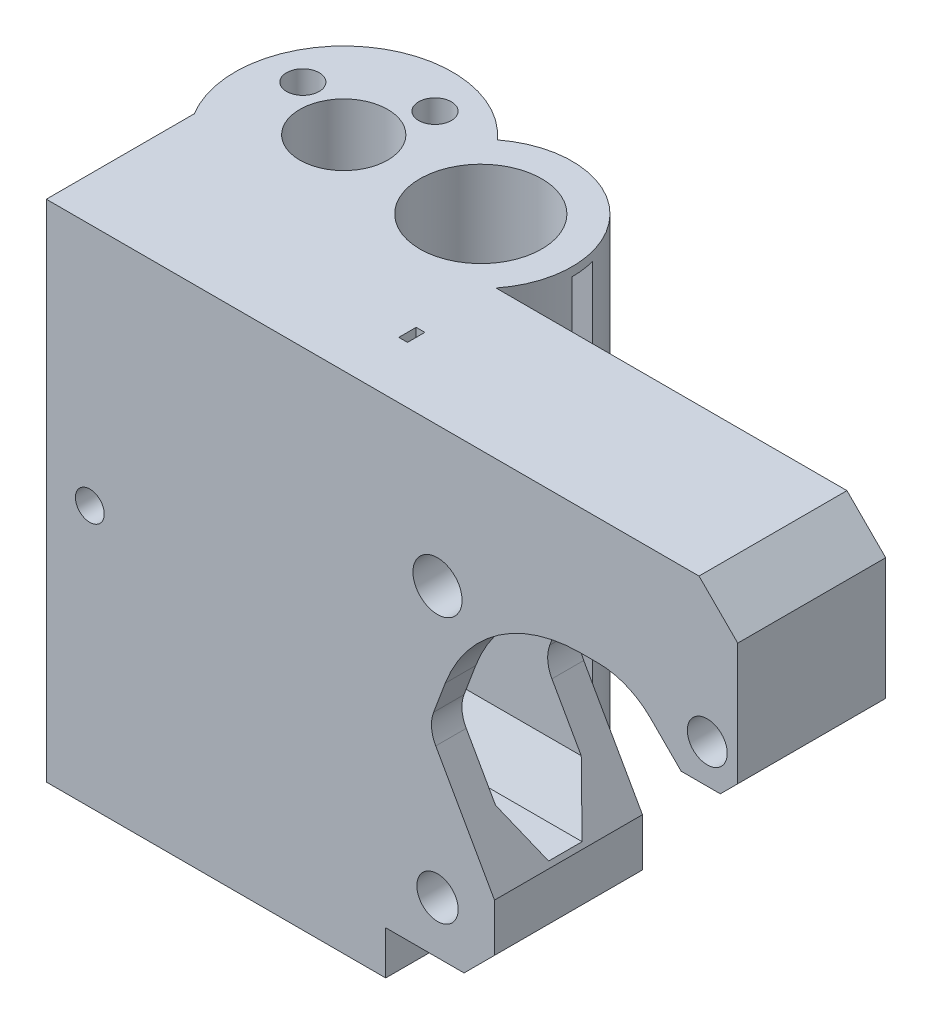
SolidWorks part; units mm, degrees
ref_plane "Front Plane" through (0, 0, 0) normal (0, 0, 1) x (1, 0, 0)
ref_plane "Top Plane" through (0, 0, 0) normal (0, 1, 0) x (1, 0, 0)
ref_plane "Right Plane" through (0, 0, 0) normal (1, 0, 0) x (0, 0, -1)
sketch "Sketch1" plane through (0, 0, 0) normal (0, 0, 1) x (1, 0, 0)
  line L0 (39, -53) -> (48, -53)
  line L1 (0, 0) -> (39, 0)
  line L2 (0, 0) -> (0, -58)
  line L3 (0, -58) -> (39, -58)
  line L4 (39, -53) -> (39, -58)
  line L5 (39, 0) -> (75, 0)
  line L6 (75, 0) -> (79.45, -4.45)
  line L7 (79.45, -4.45) -> (79.45, -18.45)
  line L8 (79.45, -18.45) -> (77.45, -20.45)
  line L9 (77.45, -20.45) -> (72.95, -20.45)
  line L10 (72.95, -20.45) -> (69.45, -16.95)
  line L12 (45.8405, -25.2376) -> (44.5009, -28.8048)
  line L13 (44.75, -32.0294) -> (51.5, -44)
  line L14 (51.5, -44) -> (51.5, -49.5)
  line L15 (61.4145, -14.45) -> (63.4145, -14.45)
  line L16 (51.5, -49.5) -> (48, -53)
  arc A5 (63.4145, -14.45) -> (69.45, -16.95) centre (63.4145, -22.9855) cw
  arc A6 (61.4145, -14.45) -> (45.8405, -25.2376) centre (61.4145, -31.0859) ccw
  arc A7 (44.5009, -28.8048) -> (44.75, -32.0294) centre (48.083, -30.15) ccw
  dimension "D1" = 58
  dimension "D2" = 39
  dimension "D3" = 75
  dimension "D4" = 4.45
  dimension "D5" = 135
  dimension "D6" = 14
  dimension "D7" = 2
  dimension "D8" = 3.5
  dimension "D9" = 6
  dimension "D10" = 5
  dimension "D11" = 4.5
  dimension "D12" = 130
  dimension "D13" = 3.5
  dimension "D14" = 5.5
  dimension "D15" = 6.75
  dimension "D16" = 9
  dimension "D17" = 13.85
  dimension "D18" = 3.417
  dimension "D19" = 2
extrude "Boss-Extrude1" add sketch "Sketch1" along normal blind 17
sketch "Sketch2" plane through (0, 0, 0) normal (0, 1, 0) x (1, 0, 0)
  line L0 (0, -17) -> (0, 6.5) construction
  line L1 (0, 6.5) -> (26.427, 6.5) construction
  circle A0 centre (26.427, 6.5) radius 10.5
  dimension "D2" = 21
  dimension "D1" = 23.5
  dimension "D3" = 26.427
extrude "Boss-Extrude2" add sketch "Sketch2" against normal up to surface (58 mm away) up to face at (19.5, -58, 8.5)
sketch "Sketch3" plane through (0, 0, 0) normal (0, 1, 0) x (1, 0, 0)
  line L0 (0, -17) -> (0, 20.4292) construction
  line L1 (10.6771, 6.5) -> (0, 6.5) construction
  line L2 (75, -17) -> (0, -17) construction
  circle A0 centre (10.6771, 6.5) radius 12.5
  dimension "D3" = 25
  dimension "D2" = 23.5
extrude "Boss-Extrude3" add sketch "Sketch3" against normal blind 13.5
sketch "Sketch4" plane through (0, 0, 0) normal (0, 1, 0) x (1, 0, 0)
  circle A0 centre (26.427, 6.5) radius 7
  circle A1 centre (10.6771, 6.5) radius 5.05
  dimension "D1" = 10.1
  dimension "D2" = 14
extrude "Cut-Extrude1" cut sketch "Sketch4" against normal through all
sketch "Sketch5" plane through (0, 0, 0) normal (-1, 0, 0) x (0, 0, 1)
  line L0 (10.5, -43.5) -> (6.65, -43.5)
  line L1 (6.65, -43.5) -> (3.65, -38)
  line L2 (3.65, -38) -> (3.65, -19)
  line L3 (3.65, -19) -> (6.65, -16)
  line L4 (6.65, -16) -> (10.5, -16)
  line L5 (10.5, -16) -> (13.5, -19)
  line L6 (13.5, -19) -> (13.5, -38)
  line L7 (13.5, -38) -> (10.5, -43.5)
  line L8 (17, 0) -> (0, 0) construction
  line L9 (17, 0) -> (17, -58) construction
  circle A0 centre (8.5, -6) radius 4.05
  circle A1 centre (8.5, -51) radius 4.05
  dimension "D8" = 8.1
  dimension "D9" = 8.1
  dimension "D1" = 19
  dimension "D2" = 3
  dimension "D3" = 3.85
  dimension "D4" = 16
  dimension "D5" = 6
  dimension "D6" = 51
  dimension "D7" = 5.5
  dimension "D10" = 3
  dimension "D11" = 3
  dimension "D12" = 19
  dimension "D13" = 3.85
  dimension "D14" = 3
  dimension "D15" = 3
  dimension "D16" = 3.5
  dimension "D17" = 8.5
  dimension "D18" = 8.5
extrude "Cut-Extrude2" cut sketch "Sketch5" against normal blind 35
sketch "Sketch6" plane through (0, 0, 0) normal (0, 0, -1) x (-1, 0, 0)
  line L0 (-75.9503, -16.0252) -> (-44.9503, -16.0252) construction
  line L1 (-44.9503, -16.0252) -> (-44.9503, -47.0252) construction
  line L2 (-44.9503, -47.0252) -> (-75.9503, -47.0252) construction
  line L3 (-75.9503, -47.0252) -> (-75.9503, -16.0252) construction
  line L4 (-75.9503, -31.5252) -> (-44.9503, -31.5252) construction
  line L5 (-60.4503, -16.0252) -> (-60.4503, -47.0252) construction
  circle A0 centre (-75.9503, -16.0252) radius 2.2933
  circle A1 centre (-44.9503, -16.0252) radius 2.8225
  circle A2 centre (-44.9503, -47.0252) radius 2.3733
  circle A3 centre (-60.4503, -31.5252) radius 11 construction
  point P14 (-60.4503, -31.5252)
  dimension "D3" = 22
  dimension "D1" = 31
  dimension "D2" = 31
extrude "Cut-Extrude3" cut sketch "Sketch6" against normal through all
sketch "Sketch8" plane through (35, 0, 0) normal (-1, 0, 0) x (0, 0, 1)
  line L8 (10.5, -43.5) -> (13.5, -38)
  line L9 (13.5, -38) -> (13.5, -19)
  line L10 (13.5, -19) -> (10.5, -16)
  line L11 (10.5, -16) -> (6.65, -16)
  line L12 (6.65, -16) -> (3.65, -19)
  line L13 (3.65, -19) -> (3.65, -38)
  line L14 (3.65, -38) -> (6.65, -43.5)
  line L15 (6.65, -43.5) -> (10.5, -43.5)
  line L16 (10.5, -43.5) -> (13.5, -38)
  line L17 (13.5, -38) -> (13.5, -19)
  line L18 (13.5, -19) -> (10.5, -16)
  line L19 (10.5, -16) -> (6.65, -16)
  line L20 (6.65, -16) -> (3.65, -19)
  line L21 (3.65, -19) -> (3.65, -38)
  line L22 (3.65, -38) -> (6.65, -43.5)
  line L23 (6.65, -43.5) -> (10.5, -43.5)
  dimension "D1" = 0
extrude "Cut-Extrude4" cut sketch "Sketch8" against normal blind 20
sketch "Sketch10" plane through (0, 0, 0) normal (0, 1, 0) x (1, 0, 0)
  line L0 (13.5702, 14.0925) -> (10.6771, 6.5) construction
  line L1 (10.6771, 6.5) -> (3.0846, 9.3931) construction
  circle A0 centre (13.5702, 14.0925) radius 1.875
  circle A1 centre (3.0846, 9.3931) radius 1.875
  dimension "D3" = 3.75
  dimension "D4" = 3.75
  dimension "D1" = 90
  dimension "D2" = 8.125
  dimension "D5" = 8.125
extrude "Cut-Extrude6" cut sketch "Sketch10" against normal through all
sketch "Sketch11" plane through (0, -58, 0) normal (0, -1, 0) x (1, 0, 0)
  line L0 (0, 17) -> (0, 0) construction
  line L1 (35, 8.5) -> (34, 8.5)
  line L2 (35, 8.5) -> (35, 10.5)
  line L3 (35, 10.5) -> (34, 10.5)
  line L4 (34, 8.5) -> (34, 10.5)
  line L5 (0, 17) -> (39, 17) construction
  dimension "D1" = 35
  dimension "D2" = 1
  dimension "D3" = 2
  dimension "D4" = 6.5
extrude "Cut-Extrude7" cut sketch "Sketch11" against normal blind 8
ref_plane "Plane1" through (0, -29, 0) normal (0, 1, 0) x (1, 0, 0)
mirror "Mirror1" about plane through (0, -29, 0) normal (0, 1, 0) of "Cut-Extrude7"
sketch "Sketch12" plane through (0, 0, 17) normal (0, 0, 1) x (1, 0, 0)
  line L0 (0, 0) -> (0, -58) construction
  line L2 (75, 0) -> (0, 0) construction
  circle A0 centre (5, -28) radius 1.6588
  dimension "D1" = 3.3175
  dimension "D2" = 5
  dimension "D3" = 28
extrude "Cut-Extrude8" cut sketch "Sketch12" against normal through all
sketch "Sketch13" plane through (0, -58, 0) normal (0, -1, 0) x (1, 0, 0)
  line L0 (26.427, -6.5) -> (36.5692, -9.2176) construction
  line L1 (26.427, -6.5) -> (9.2701, -6.5) construction
  line L2 (26.427, -6.5) -> (36.927, -6.5) construction
  line L3 (33.1885, -8.3117) -> (36.5692, -9.2176)
  line L4 (36.927, -6.5) -> (33.427, -6.5)
  arc A0 (33.1885, -8.3117) -> (33.427, -6.5) centre (26.427, -6.5) ccw
  arc A1 (15.927, -6.5) -> (36.927, -6.5) centre (26.427, -6.5) ccw construction
  arc A2 (18.1808, 0) -> (34.6732, 0) centre (26.427, -6.5) ccw construction
  circle A3 centre (26.427, -6.5) radius 7 construction
  point P7 (0, 0)
  point P8 (26.427, -6.5)
  point P15 (15.2103, 4.7167)
  point P16 (36.5692, -9.2176)
  dimension "D1" = 15
  dimension "D2" = 180
extrude "Cut-Extrude9" cut sketch "Sketch13" against normal blind 57 and the other way through all
